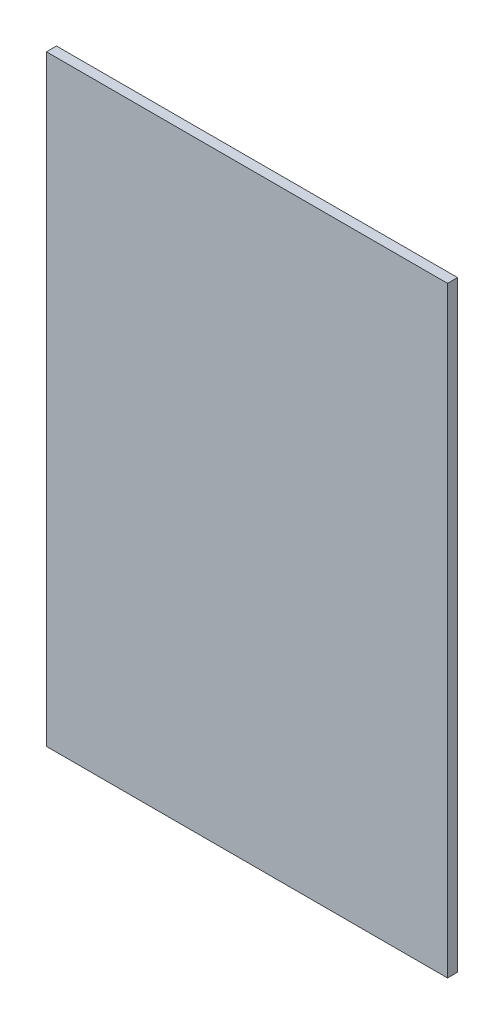
SolidWorks part; units mm, degrees
ref_plane "Plan de face" through (0, 0, 0) normal (0, 0, 1) x (1, 0, 0)
ref_plane "Plan de dessus" through (0, 0, 0) normal (0, 1, 0) x (1, 0, 0)
ref_plane "Plan de droite" through (0, 0, 0) normal (1, 0, 0) x (0, 0, -1)
sketch "Esquisse1" plane through (0, 0, 0) normal (0, 0, 1) x (1, 0, 0)
  line L2 (0, 0) -> (-400, 0)
  line L3 (0, 0) -> (0, 600)
  line L4 (0, 600) -> (-400, 600)
  line L5 (-400, 0) -> (-400, 600)
  dimension "D1" = 400
  dimension "D2" = 600
extrude "Boss.-Extru.1" add sketch "Esquisse1" against normal blind 10
